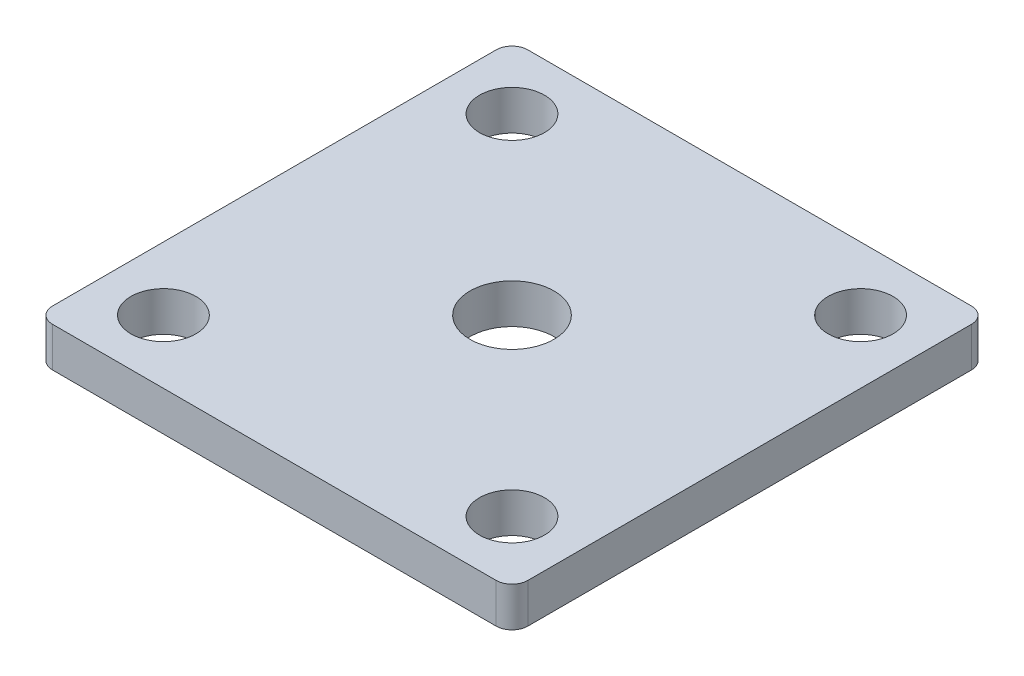
SolidWorks part; units mm, degrees
material "Acrylic (Medium-high impact)"
ref_plane "Front" through (0, 0, 0) normal (0, 0, 1) x (1, 0, 0)
ref_plane "Top" through (0, 0, 0) normal (0, 1, 0) x (1, 0, 0)
ref_plane "Right" through (0, 0, 0) normal (1, 0, 0) x (0, 0, -1)
sketch "Sketch1" plane through (0, 0, 0) normal (0, 0, 1) x (1, 0, 0)
  line L0 (-22.225, 0) -> (22.225, 0)
  dimension "D1" = 44.45
sketch "Sketch2" plane through (0, 0, 0) normal (0, 1, 0) x (1, 0, 0)
  line L0 (-13.97, 13.97) -> (13.97, 13.97) construction
  line L1 (-13.97, 13.97) -> (-13.97, -13.97) construction
  line L2 (-13.97, -13.97) -> (13.97, -13.97) construction
  line L3 (13.97, 13.97) -> (13.97, -13.97) construction
  line L4 (-13.97, 13.97) -> (13.97, -13.97) construction
  line L5 (-13.97, -13.97) -> (13.97, 13.97) construction
  line L7 (-19.05, 19.05) -> (19.05, 19.05)
  line L8 (-19.05, 19.05) -> (-19.05, -19.05)
  line L9 (-19.05, -19.05) -> (19.05, -19.05)
  line L10 (19.05, 19.05) -> (19.05, -19.05)
  line L11 (-19.05, 19.05) -> (19.05, -19.05) construction
  line L12 (-19.05, -19.05) -> (19.05, 19.05) construction
  circle A0 centre (-13.97, 13.97) radius 2.6035
  circle A1 centre (-13.97, -13.97) radius 2.6035
  circle A2 centre (13.97, -13.97) radius 2.6035
  circle A3 centre (13.97, 13.97) radius 2.6035
  circle A4 centre (0, 0) radius 3.3655
  point P0 (0, 0)
  point P12 (0, 0)
  dimension "D3" = 5.207
  dimension "D5" = 6.731
  dimension "D1" = 27.94
  dimension "D2" = 27.94
  dimension "D4" = 38.1
extrude "Boss-Extrude1" add sketch "Sketch2" along normal blind 3.175
fillet "Fillet1" radius 1.27 4 edges at (-19.05, 1.5875, -19.05) (19.05, 1.5875, -19.05) (19.05, 1.5875, 19.05) (-19.05, 1.5875, 19.05)
